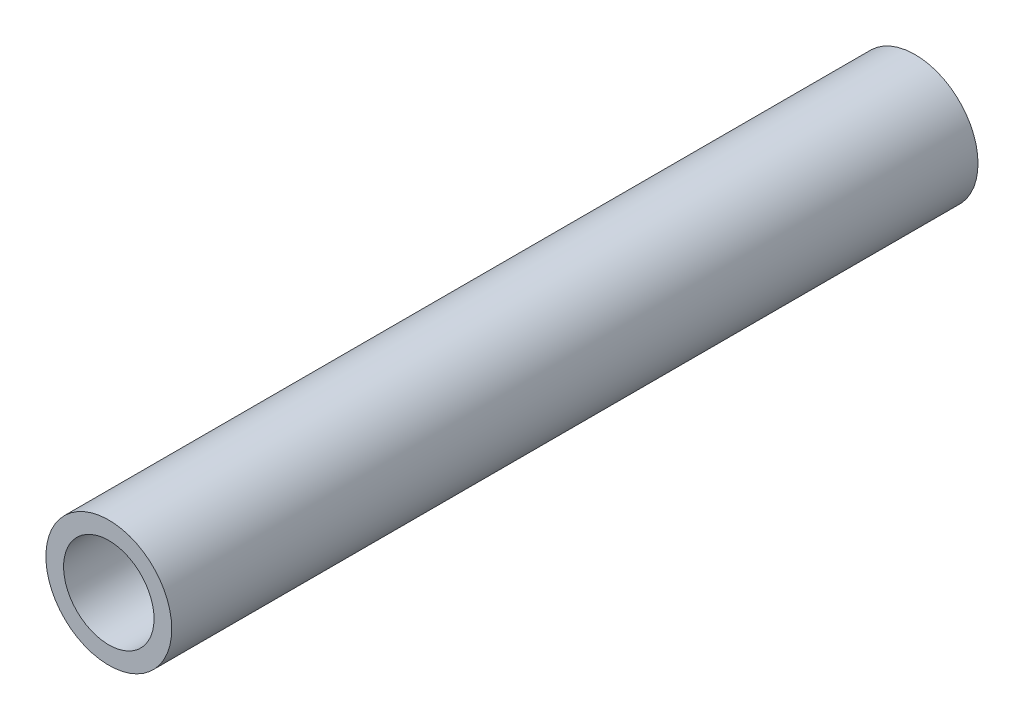
SolidWorks part; units mm, degrees
material "Acciaio inossidabile fuso"
ref_plane "Piano frontale" through (0, 0, 0) normal (0, 0, 1) x (1, 0, 0)
ref_plane "Piano superiore" through (0, 0, 0) normal (0, 1, 0) x (1, 0, 0)
ref_plane "Piano destro" through (0, 0, 0) normal (1, 0, 0) x (0, 0, -1)
sketch "Schizzo1" plane through (0, 0, 0) normal (0, 0, 1) x (1, 0, 0)
  circle A0 centre (0, 0) radius 3.2
  dimension "D1" = 6.4
extrude "Estrusione-Sottile1" add sketch "Schizzo1" along normal blind 41 thin thin type one direction reverse wall 0.9
